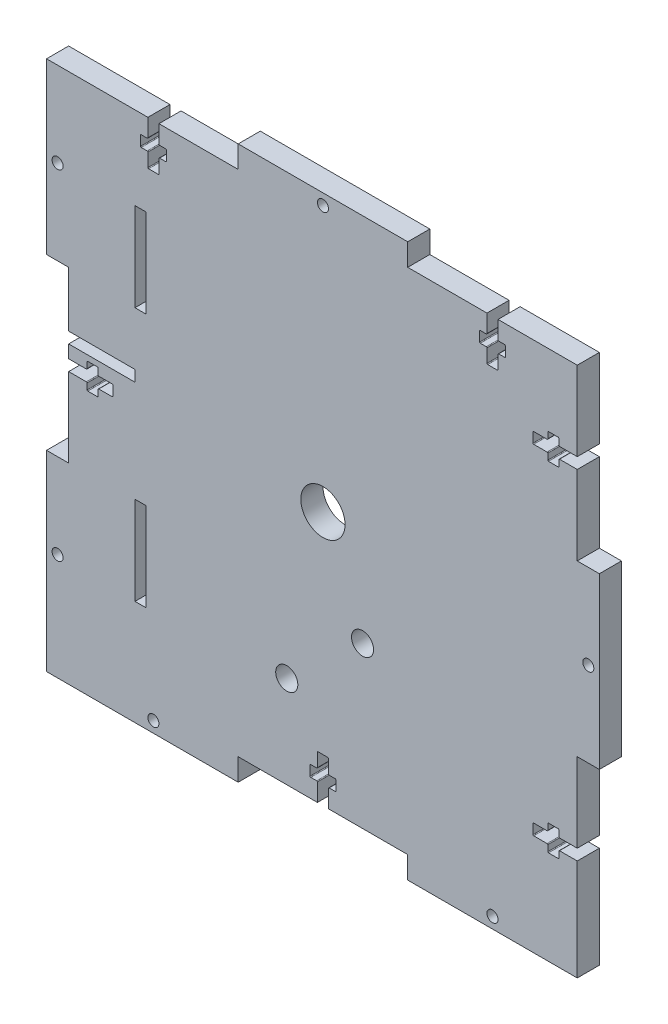
SolidWorks part; units mm, degrees
ref_plane "Front Plane" through (0, 0, 0) normal (0, 0, 1) x (1, 0, 0)
ref_plane "Top Plane" through (0, 0, 0) normal (0, 1, 0) x (1, 0, 0)
ref_plane "Right Plane" through (0, 0, 0) normal (1, 0, 0) x (0, 0, -1)
sketch "Sketch1" plane through (0, 0, 0) normal (0, 0, 1) x (1, 0, 0)
  line L0 (-69, 69) -> (-23, 69)
  line L5 (-75, -75) -> (75, -75) construction
  line L6 (-75, -75) -> (-75, 75) construction
  line L7 (-75, 75) -> (75, 75) construction
  line L8 (75, -75) -> (75, 75) construction
  line L9 (75, 23) -> (69, 23)
  line L10 (69, -23) -> (75, -23)
  line L11 (-69, -69) -> (69, -69) construction
  line L12 (-69, -69) -> (-69, 69) construction
  line L13 (-69, 69) -> (69, 69) construction
  line L14 (69, -69) -> (69, 69) construction
  line L15 (-69, -69) -> (69, 69) construction
  line L16 (69, -69) -> (69, -23)
  line L17 (-23, 69) -> (-23, 75)
  line L18 (-23, 75) -> (23, 75)
  line L19 (23, 75) -> (23, 69)
  line L20 (23, 69) -> (69, 69)
  line L21 (75, -23) -> (75, 23)
  line L22 (69, 23) -> (69, 69)
  line L23 (-75, 23) -> (-69, 23)
  line L24 (-69, 69) -> (-75, 69)
  line L25 (-75, 69) -> (-75, 23)
  line L26 (69, -69) -> (69, -75)
  line L27 (69, -75) -> (23, -75)
  line L28 (23, -75) -> (23, -69)
  line L29 (23, -69) -> (-23, -69)
  line L30 (-23, -69) -> (-23, -75)
  line L31 (-23, -75) -> (-69, -75)
  line L32 (-69, -75) -> (-69, -69) construction
  line L33 (-69, 23) -> (-69, -23)
  line L34 (-69, -23) -> (-75, -23)
  line L35 (-75, -23) -> (-75, -69)
  line L36 (-75, -69) -> (-69, -69) construction
  line L37 (-46, 69) -> (-46, -75) construction
  line L38 (-69, 69) -> (69, -69) construction
  line L39 (-75, -75) -> (-69, -75)
  line L40 (-75, -75) -> (-75, -69)
  point P0 (0, 0)
  point P6 (-7, -7)
  point P26 (0, -75)
  point P27 (-75, 0)
  dimension "D1" = 150
  dimension "D2" = 150
  dimension "D5" = 46
  dimension "D3" = 6
  dimension "D6" = 6
  dimension "D7" = 6
extrude "Box Side" add sketch "Sketch1" along normal blind 6
sketch "Sketch2" plane through (0, 0, 6) normal (0, 0, 1) x (1, 0, 0)
  line L0 (23, 72) -> (-23, 72) construction
  line L1 (23, 75) -> (23, 69) construction
  line L2 (-23, 69) -> (-23, 75) construction
  line L3 (-46, 69) -> (-46, -75) construction
  line L5 (0, 75) -> (0, 69) construction
  line L6 (-23, 75) -> (23, 75) construction
  line L7 (-69, 69) -> (69, 69) construction
  line L16 (-46, 69) -> (-46, -75) construction
  line L21 (0, -69) -> (0, 69) construction
  line L35 (-69, 69) -> (-23, 69) construction
  line L36 (-44.5, 69) -> (-44.5, 64.2)
  line L37 (-44.3, 64) -> (-42.7, 64)
  line L38 (-42.5, 63.8) -> (-42.5, 61.2)
  line L39 (-42.7, 61) -> (-44.3, 61)
  line L40 (-44.5, 60.8) -> (-44.5, 57.2)
  line L46 (-44.7, 57) -> (-47.3, 57)
  line L48 (-44.5, 69) -> (-47.5, 69)
  line L51 (-47.5, 60.8) -> (-47.5, 57.2)
  line L52 (-49.3, 61) -> (-47.7, 61)
  line L53 (-49.5, 63.8) -> (-49.5, 61.2)
  line L54 (-47.7, 64) -> (-49.3, 64)
  line L55 (-47.5, 69) -> (-47.5, 64.2)
  line L56 (47.5, 69) -> (47.5, 64.2)
  line L57 (47.7, 64) -> (49.3, 64)
  line L58 (49.5, 63.8) -> (49.5, 61.2)
  line L59 (49.3, 61) -> (47.7, 61)
  line L60 (47.5, 60.8) -> (47.5, 57.2)
  line L61 (44.5, 69) -> (47.5, 69)
  line L62 (44.7, 57) -> (47.3, 57)
  line L63 (44.5, 60.8) -> (44.5, 57.2)
  line L64 (42.7, 61) -> (44.3, 61)
  line L65 (42.5, 63.8) -> (42.5, 61.2)
  line L66 (44.3, 64) -> (42.7, 64)
  line L67 (44.5, 69) -> (44.5, 64.2)
  line L68 (-69, -69) -> (69, 69) construction
  line L69 (-69, -69) -> (69, 69) construction
  line L70 (75, 0) -> (69, 0) construction
  line L71 (72, 23) -> (72, -23) construction
  line L72 (69, 44.5) -> (64.2, 44.5)
  line L73 (64, 44.3) -> (64, 42.7)
  line L74 (63.8, 42.5) -> (61.2, 42.5)
  line L75 (61, 42.7) -> (61, 44.3)
  line L76 (60.8, 44.5) -> (57.2, 44.5)
  line L77 (57, 44.7) -> (57, 47.3)
  line L78 (69, 44.5) -> (69, 47.5)
  line L79 (60.8, 47.5) -> (57.2, 47.5)
  line L80 (61, 49.3) -> (61, 47.7)
  line L81 (63.8, 49.5) -> (61.2, 49.5)
  line L82 (64, 47.7) -> (64, 49.3)
  line L83 (69, 47.5) -> (64.2, 47.5)
  line L84 (69, -47.5) -> (64.2, -47.5)
  line L85 (64, -47.7) -> (64, -49.3)
  line L86 (63.8, -49.5) -> (61.2, -49.5)
  line L87 (61, -49.3) -> (61, -47.7)
  line L88 (60.8, -47.5) -> (57.2, -47.5)
  line L89 (69, -44.5) -> (69, -47.5)
  line L90 (57, -44.7) -> (57, -47.3)
  line L91 (60.8, -44.5) -> (57.2, -44.5)
  line L92 (61, -42.7) -> (61, -44.3)
  line L93 (63.8, -42.5) -> (61.2, -42.5)
  line L94 (64, -44.3) -> (64, -42.7)
  line L95 (69, -44.5) -> (64.2, -44.5)
  line L120 (-69, 69) -> (69, -69) construction
  line L121 (-69, 69) -> (69, -69) construction
  line L122 (-1.5, -69) -> (1.5, -69)
  line L123 (-23, -69) -> (23, -69) construction
  line L124 (1.5, -69) -> (1.5, -64.2)
  line L125 (1.7, -64) -> (3.3, -64)
  line L126 (3.5, -63.8) -> (3.5, -61.2)
  line L127 (3.3, -61) -> (1.7, -61)
  line L128 (1.5, -60.8) -> (1.5, -57.2)
  line L129 (1.3, -57) -> (-1.3, -57)
  line L130 (-1.5, -60.8) -> (-1.5, -57.2)
  line L131 (-3.3, -61) -> (-1.7, -61)
  line L132 (-3.5, -63.8) -> (-3.5, -61.2)
  line L133 (-1.7, -64) -> (-3.3, -64)
  line L134 (-1.5, -69) -> (-1.5, -64.2)
  line L135 (-69, -1.5) -> (-64.2, -1.5)
  line L136 (-64, -1.7) -> (-64, -3.3)
  line L137 (-63.8, -3.5) -> (-61.2, -3.5)
  line L138 (-61, -3.3) -> (-61, -1.7)
  line L139 (-60.8, -1.5) -> (-57.2, -1.5)
  line L140 (-57, 1.3) -> (-57, -1.3)
  line L141 (-60.8, 1.5) -> (-57.2, 1.5)
  line L142 (-61, 3.3) -> (-61, 1.7)
  line L143 (-63.8, 3.5) -> (-61.2, 3.5)
  line L144 (-64, 1.7) -> (-64, 3.3)
  line L145 (-69, 1.5) -> (-64.2, 1.5)
  line L146 (-69, -1.5) -> (-69, 1.5)
  line L147 (-69, -72) -> (-23, -72) construction
  line L148 (-23, 69) -> (-75, 69) construction
  line L149 (-23, -75) -> (-23, -69) construction
  line L150 (-69, -69) -> (-69, -75) construction
  line L151 (-75, -75) -> (-23, -75) construction
  circle A0 centre (0, 72) radius 1.5
  arc A1 (-44.5, 57.2) -> (-44.7, 57) centre (-44.7, 57.2) cw
  arc A2 (-44.3, 61) -> (-44.5, 60.8) centre (-44.3, 60.8) ccw
  arc A3 (-42.5, 61.2) -> (-42.7, 61) centre (-42.7, 61.2) cw
  arc A4 (-42.7, 64) -> (-42.5, 63.8) centre (-42.7, 63.8) cw
  arc A5 (-44.5, 64.2) -> (-44.3, 64) centre (-44.3, 64.2) ccw
  arc A6 (-47.5, 64.2) -> (-47.7, 64) centre (-47.7, 64.2) cw
  arc A7 (-49.3, 64) -> (-49.5, 63.8) centre (-49.3, 63.8) ccw
  arc A8 (-49.5, 61.2) -> (-49.3, 61) centre (-49.3, 61.2) ccw
  arc A9 (-47.7, 61) -> (-47.5, 60.8) centre (-47.7, 60.8) cw
  arc A10 (-47.5, 57.2) -> (-47.3, 57) centre (-47.3, 57.2) ccw
  arc A11 (47.5, 57.2) -> (47.3, 57) centre (47.3, 57.2) cw
  arc A12 (47.7, 61) -> (47.5, 60.8) centre (47.7, 60.8) ccw
  arc A13 (49.5, 61.2) -> (49.3, 61) centre (49.3, 61.2) cw
  arc A14 (49.3, 64) -> (49.5, 63.8) centre (49.3, 63.8) cw
  arc A15 (47.5, 64.2) -> (47.7, 64) centre (47.7, 64.2) ccw
  arc A16 (44.5, 64.2) -> (44.3, 64) centre (44.3, 64.2) cw
  arc A17 (42.7, 64) -> (42.5, 63.8) centre (42.7, 63.8) ccw
  arc A18 (42.5, 61.2) -> (42.7, 61) centre (42.7, 61.2) ccw
  arc A19 (44.3, 61) -> (44.5, 60.8) centre (44.3, 60.8) cw
  arc A20 (44.5, 57.2) -> (44.7, 57) centre (44.7, 57.2) ccw
  arc A21 (57.2, 44.5) -> (57, 44.7) centre (57.2, 44.7) cw
  arc A22 (61, 44.3) -> (60.8, 44.5) centre (60.8, 44.3) ccw
  arc A23 (61.2, 42.5) -> (61, 42.7) centre (61.2, 42.7) cw
  arc A24 (64, 42.7) -> (63.8, 42.5) centre (63.8, 42.7) cw
  arc A25 (64.2, 44.5) -> (64, 44.3) centre (64.2, 44.3) ccw
  arc A26 (64.2, 47.5) -> (64, 47.7) centre (64.2, 47.7) cw
  arc A27 (64, 49.3) -> (63.8, 49.5) centre (63.8, 49.3) ccw
  arc A28 (61.2, 49.5) -> (61, 49.3) centre (61.2, 49.3) ccw
  arc A29 (61, 47.7) -> (60.8, 47.5) centre (60.8, 47.7) cw
  arc A30 (57.2, 47.5) -> (57, 47.3) centre (57.2, 47.3) ccw
  arc A31 (57.2, -47.5) -> (57, -47.3) centre (57.2, -47.3) cw
  arc A32 (61, -47.7) -> (60.8, -47.5) centre (60.8, -47.7) ccw
  arc A33 (61.2, -49.5) -> (61, -49.3) centre (61.2, -49.3) cw
  arc A34 (64, -49.3) -> (63.8, -49.5) centre (63.8, -49.3) cw
  arc A35 (64.2, -47.5) -> (64, -47.7) centre (64.2, -47.7) ccw
  arc A36 (64.2, -44.5) -> (64, -44.3) centre (64.2, -44.3) cw
  arc A37 (64, -42.7) -> (63.8, -42.5) centre (63.8, -42.7) ccw
  arc A38 (61.2, -42.5) -> (61, -42.7) centre (61.2, -42.7) ccw
  arc A39 (61, -44.3) -> (60.8, -44.5) centre (60.8, -44.3) cw
  arc A40 (57.2, -44.5) -> (57, -44.7) centre (57.2, -44.7) ccw
  circle A41 centre (72, 0) radius 1.5
  arc A62 (1.5, -57.2) -> (1.3, -57) centre (1.3, -57.2) ccw
  arc A63 (1.7, -61) -> (1.5, -60.8) centre (1.7, -60.8) cw
  arc A64 (3.5, -61.2) -> (3.3, -61) centre (3.3, -61.2) ccw
  arc A65 (3.3, -64) -> (3.5, -63.8) centre (3.3, -63.8) ccw
  arc A66 (1.5, -64.2) -> (1.7, -64) centre (1.7, -64.2) cw
  arc A67 (-1.5, -64.2) -> (-1.7, -64) centre (-1.7, -64.2) ccw
  arc A68 (-3.3, -64) -> (-3.5, -63.8) centre (-3.3, -63.8) cw
  arc A69 (-3.5, -61.2) -> (-3.3, -61) centre (-3.3, -61.2) cw
  arc A70 (-1.7, -61) -> (-1.5, -60.8) centre (-1.7, -60.8) ccw
  arc A71 (-1.5, -57.2) -> (-1.3, -57) centre (-1.3, -57.2) cw
  arc A72 (-57.2, -1.5) -> (-57, -1.3) centre (-57.2, -1.3) ccw
  arc A73 (-61, -1.7) -> (-60.8, -1.5) centre (-60.8, -1.7) cw
  arc A74 (-61.2, -3.5) -> (-61, -3.3) centre (-61.2, -3.3) ccw
  arc A75 (-64, -3.3) -> (-63.8, -3.5) centre (-63.8, -3.3) ccw
  arc A76 (-64.2, -1.5) -> (-64, -1.7) centre (-64.2, -1.7) cw
  arc A77 (-64.2, 1.5) -> (-64, 1.7) centre (-64.2, 1.7) ccw
  arc A78 (-64, 3.3) -> (-63.8, 3.5) centre (-63.8, 3.3) cw
  arc A79 (-61.2, 3.5) -> (-61, 3.3) centre (-61.2, 3.3) cw
  arc A80 (-61, 1.7) -> (-60.8, 1.5) centre (-60.8, 1.7) ccw
  arc A81 (-57.2, 1.5) -> (-57, 1.3) centre (-57.2, 1.3) cw
  circle A82 centre (-46, -72) radius 1.5
  circle A83 centre (46, -72) radius 1.5
  circle A84 centre (-72, 46) radius 1.5
  circle A85 centre (-72, -46) radius 1.5
  point P6 (0, 72)
  point P38 (0, 0)
  point P56 (-46, 57)
  point P88 (46, 57)
  point P161 (57, 46)
  point P162 (57, -46)
  point P198 (0, -57)
  point P231 (-57, 0)
  point P234 (-42.5, 62.5)
  dimension "D1" = 3
  dimension "D2" = 0.2
  dimension "D8" = 0.2
  dimension "D14" = 3
  dimension "D4" = 3
  dimension "D7" = 1.5
  dimension "D10" = 3
  dimension "D12" = 1.5
  dimension "D9" = 12
  dimension "D11" = 5
  dimension "D13" = 7
  dimension "D3" = 12
  dimension "D5" = 7
  dimension "D6" = 5
extrude "Screw Cut-outs" cut sketch "Sketch2" against normal through all
sketch "Sketch3" plane through (0, 0, 6) normal (0, 0, 1) x (1, 0, 0)
  line L0 (-69, -69) -> (69, 69) construction
  line L1 (-69, -69) -> (69, 69) construction
  line L2 (-69, 69) -> (69, -69) construction
  line L3 (-69, 69) -> (69, -69) construction
  circle A0 centre (0, 0) radius 6
  point P4 (0, 0)
  dimension "D1" = 12
extrude "BearingHole" cut sketch "Sketch3" against normal through all
sketch "Sketch4" plane through (0, 0, 6) normal (0, 0, 1) x (1, 0, 0)
  line L0 (-69, 23) -> (-69, 1.5) construction
  line L1 (-69, 5) -> (-51, 5)
  line L2 (-69, 5) -> (-69, 8)
  line L3 (-69, 8) -> (-51, 8)
  line L4 (-51, 5) -> (-51, 8)
  line L5 (-61.2, 3.5) -> (-63.8, 3.5) construction
  line L6 (-75, -23) -> (-75, -75) construction
  line L7 (-51, 46.5) -> (-48, 46.5)
  line L8 (-51, 46.5) -> (-51, 22.5)
  line L9 (-51, 22.5) -> (-48, 22.5)
  line L10 (-48, 46.5) -> (-48, 22.5)
  line L11 (-51, -22.5) -> (-48, -22.5)
  line L12 (-51, -22.5) -> (-51, -46.5)
  line L13 (-51, -46.5) -> (-48, -46.5)
  line L14 (-48, -22.5) -> (-48, -46.5)
  line L15 (-47.5, 69) -> (-75, 69) construction
  dimension "D1" = 3
  dimension "D2" = 1.5
  dimension "D3" = 18
  dimension "D4" = 3
  dimension "D5" = 24
  dimension "D6" = 24
  dimension "D7" = 22.5
  dimension "D8" = 45
extrude "Grooves" cut sketch "Sketch4" against normal up to surface (6 mm away) up to face at (6, 0, 0)
sketch "Sketch5" plane through (0, 0, 6) normal (0, 0, 1) x (1, 0, 0)
  line L0 (1.5, -69) -> (23, -69) construction
  line L3 (-75, -23) -> (-75, -75) construction
  circle A0 centre (-9.82, -44) radius 3
  dimension "D1" = 6
  dimension "D3" = 65.18
  dimension "D2" = 25
extrude "clockwiseShaftHole" cut sketch "Sketch5" against normal through all
sketch "Sketch6" plane through (0, 0, 0) normal (0, 0, -1) x (-1, 0, 0)
  circle A0 centre (-10.75, -25.5) radius 3
  circle A1 centre (0, 0) radius 19.385 construction
  circle A2 centre (9.82, -44) radius 19.385 construction
  circle A3 centre (-10.75, -25.5) radius 10.19 construction
  dimension "D1" = 6
  dimension "D4" = 38.77
  dimension "D5" = 20.38
  dimension "D2" = 25.5
  dimension "D3" = 10.75
extrude "Cut-Extrude1" cut sketch "Sketch6" against normal through all
equation "\"filletRadius\"=0.2"
equation "\"D8@Sketch2\"=\"filletRadius\""
equation "\"D2@Sketch2\"=\"filletRadius\""
equation "\"fingerWidth\"= 46"
equation "\"D5@Sketch1\"=\"fingerWidth\""
equation "\"wallThickness\"= 6"
equation "\"D3@Sketch1\" = \"wallThickness\""
equation "\"D6@Sketch1\" = \"wallThickness\""
equation "\"D7@Sketch1\" = \"wallThickness\""
equation "\"D1@Box Side\" = \"wallThickness\""
equation "\"M3\"= 3"
equation "\"D14@Sketch2\"=\"M3\""
equation "\"D1@Sketch2\"=\"M3\""
equation "\"D12@Sketch2\"=\"M3\"/2"
equation "\"nutThickness\"=3"
equation "\"D10@Sketch2\" = \"nutThickness\""
equation "\"boltLength\"= 12"
equation "\"D9@Sketch2\" = \"boltLength\""
equation "\"distanceToNut\"= 5"
equation "\"D11@Sketch2\" = \"distanceToNut\""
equation "\"D13@Sketch2\" = \"nutWidth\""
equation "\"D7@Sketch2\"=\"M3\"/2"
equation "\"D4@Sketch2\" = \"nutThickness\""
equation "\"D3@Sketch2\" = \"boltLength\""
equation "\"D5@Sketch2\" = \"nutWidth\""
equation "\"D6@Sketch2\" = \"distanceToNut\""
equation "\"sideLength\"=150"
equation "\"D1@Sketch1\"=\"sideLength\""
equation "\"D2@Sketch1\"=\"sideLength\""
equation "\"nutWidth\"=7"
